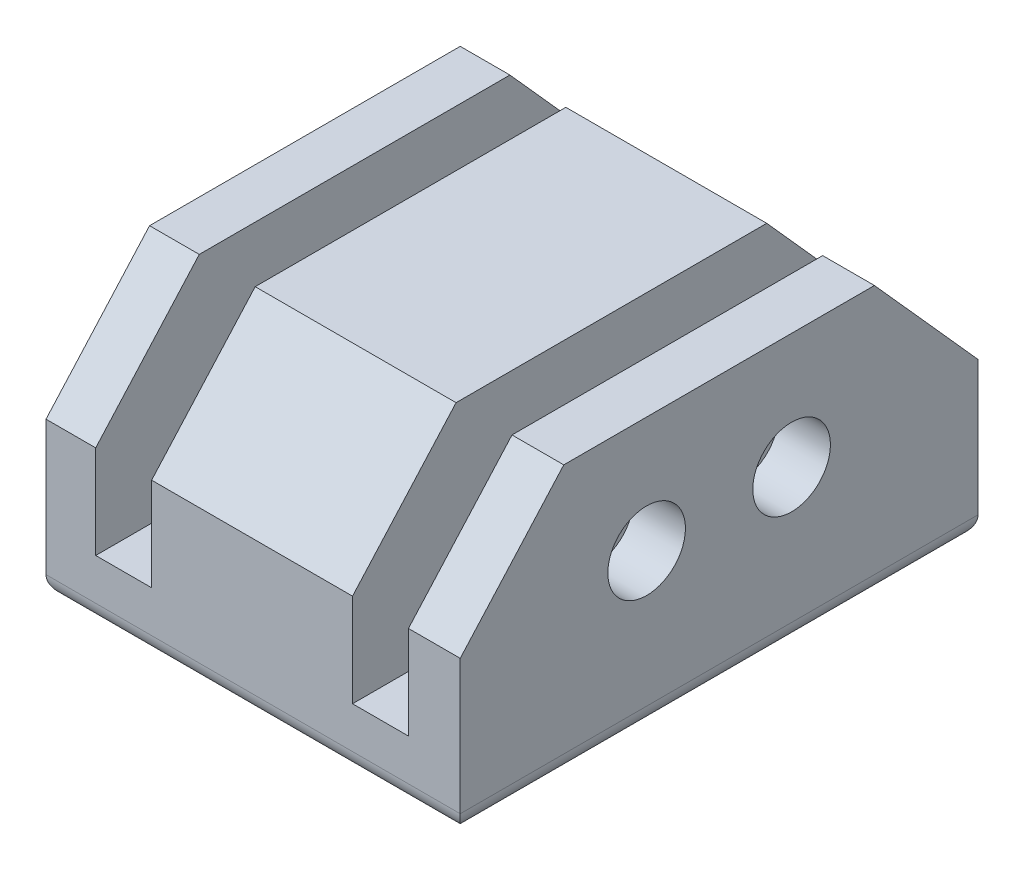
SolidWorks part; units mm, degrees
ref_plane "Front Plane" through (0, 0, 0) normal (0, 0, 1) x (1, 0, 0)
ref_plane "Top Plane" through (0, 0, 0) normal (0, 1, 0) x (1, 0, 0)
ref_plane "Right Plane" through (0, 0, 0) normal (1, 0, 0) x (0, 0, -1)
sketch "Sketch1" plane through (0, 0, 0) normal (1, 0, 0) x (0, 0, -1)
  line L1 (0, 0) -> (63.5, 0)
  line L2 (0, 0) -> (0, 6.35)
  line L3 (0, 6.35) -> (63.5, 6.35)
  line L4 (63.5, 0) -> (63.5, 6.35)
  dimension "D1" = 6.35
  dimension "D2" = 63.5
extrude "Boss-Extrude1" add sketch "Sketch1" against normal blind 50.8
sketch "Sketch2" plane through (0, 0, 0) normal (1, 0, 0) x (0, 0, -1)
  line L0 (0, 6.35) -> (0, 19.05)
  line L1 (0, 19.05) -> (12.7, 33.249)
  line L2 (12.7, 33.249) -> (50.8, 33.249)
  line L3 (50.8, 33.249) -> (63.5, 19.05)
  line L4 (63.5, 19.05) -> (63.5, 6.35)
  line L5 (63.5, 6.35) -> (0, 6.35)
  point P7 (31.75, 33.249)
  point P10 (31.75, 6.35)
  dimension "D1" = 38.1
  dimension "D2" = 12.7
  dimension "D3" = 12.7
  dimension "D4" = 19.05
  dimension "D5" = 19.05
extrude "Boss-Extrude2" add sketch "Sketch2" against normal blind 50.8
sketch "Sketch10" plane through (0, 0, -63.5) normal (0, 0, -1) x (-1, 0, 0)
  line L1 (50.8, 33.249) -> (0, 33.249) construction
  line L3 (6.35, 7.62) -> (6.35, 33.249)
  line L4 (6.35, 33.249) -> (13.208, 33.249)
  line L5 (13.208, 7.62) -> (13.208, 33.249)
  line L6 (6.35, 7.62) -> (13.208, 7.62)
  line L8 (50.8, 0) -> (0, 0) construction
  point P11 (13.208, 7.62)
  dimension "D1" = 7.62
  dimension "D2" = 6.858
  dimension "D3" = 6.35
extrude "Cut-Extrude1" cut sketch "Sketch10" against normal through all
pattern_linear "LPattern3" count 2 spacing 31.496 along (-1, 0, 0) of "Cut-Extrude1"
sketch "Sketch11" plane through (0, 0, 0) normal (1, 0, 0) x (0, 0, -1)
  circle A0 centre (22.86, 19.05) radius 4.7625
  circle A1 centre (22.86, 19.05) radius 7.9375 construction
  circle A2 centre (40.64, 19.05) radius 4.7625
  circle A3 centre (40.64, 19.05) radius 7.9375 construction
  dimension "D1" = 9.525
  dimension "D3" = 15.875
  dimension "D4" = 9.525
  dimension "D6" = 15.875
  dimension "D2" = 10.16
  dimension "D5" = 10.16
extrude "Cut-Extrude2" cut sketch "Sketch11" against normal through all
sketch "Sketch14" plane through (0, 33.249, 0) normal (0, 1, 0) x (1, 0, 0)
  line L3 (-37.846, 12.7) -> (-37.846, 50.8) construction
  point P0 (-25.4, 31.75)
  point P4 (-37.846, 31.75)
  dimension "D1" = 12.446
sketch "Sketch17" plane through (0, 40.0201, -44.7438) normal (0, 0.6667, -0.7454) x (-1, 0, 0)
  line L0 (13.208, -28.1343) -> (13.208, -9.0843) construction
  line L1 (37.846, -9.0843) -> (13.208, -9.0843) construction
  point P0 (25.527, -18.6093)
  point P4 (13.208, -18.6093)
  point P7 (25.527, -9.0843)
sketch "Sketch18" plane through (0, 8.4667, 9.466) normal (0, 0.6667, 0.7454) x (1, 0, 0)
  line L0 (-13.208, 33.249) -> (-13.208, 14.199) construction
  line L1 (-37.846, 33.249) -> (-13.208, 33.249) construction
  point P0 (-25.527, 23.724)
  point P1 (-25.527, 23.724)
  point P4 (-13.208, 23.724)
  point P7 (-25.527, 33.249)
ref_plane "Plane2" through (0, 33.02, 0) normal (0, -1, 0) x (-1, 0, 0)
ref_plane "midplane" through (0, 0, -31.75) normal (0, 0, -1) x (-1, 0, 0)
fillet "Fillet1" radius 2.54 4 edges at (0, 0, -31.75) (-25.4, 0, -63.5) (-50.8, 0, -31.75) (-25.4, 0, 0)
sketch "Sketch19" plane through (0, 0, 0) normal (0, -1, 0) x (1, 0, 0)
  line L0 (-25.4, -63.5) -> (-25.4, 0) construction
  line L1 (0, -63.5) -> (-50.8, -63.5) construction
  line L2 (-50.8, 0) -> (0, 0) construction
  line L3 (0, -31.75) -> (-50.8, -31.75) construction
  line L4 (0, 0) -> (0, -63.5) construction
  line L5 (-50.8, -63.5) -> (-50.8, 0) construction
  line L7 (-9.525, -50.8) -> (-41.275, -50.8) construction
  line L8 (-9.525, -50.8) -> (-9.525, -12.7) construction
  line L9 (-9.525, -12.7) -> (-41.275, -12.7) construction
  line L10 (-41.275, -50.8) -> (-41.275, -12.7) construction
  line L11 (-9.525, -50.8) -> (-41.275, -12.7) construction
  line L12 (-9.525, -12.7) -> (-41.275, -50.8) construction
  circle A0 centre (-9.525, -50.8) radius 1.778
  circle A1 centre (-41.275, -50.8) radius 1.778
  circle A2 centre (-41.275, -12.7) radius 1.778
  circle A3 centre (-9.525, -12.7) radius 1.778
  point P12 (-25.4, -31.75)
  dimension "D3" = 3.556
  dimension "D1" = 31.75
  dimension "D2" = 38.1
extrude "Cut-Extrude3" cut sketch "Sketch19" against normal up to surface (7.62 mm away) up to face at (-9.779, 7.62, -31.75)
